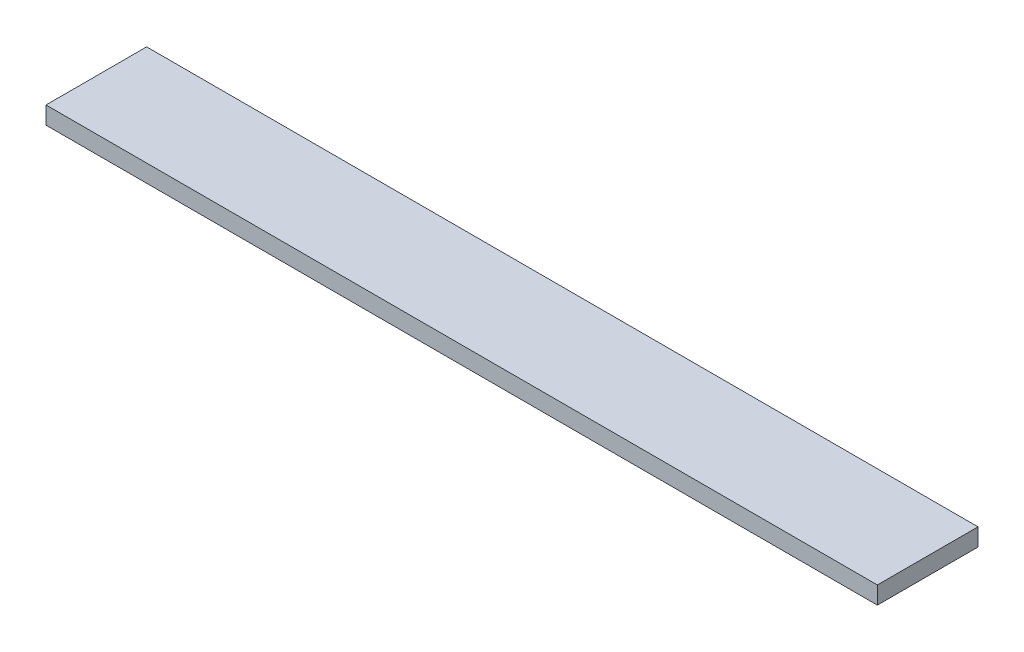
SolidWorks part; units mm, degrees
ref_plane "Front" through (0, 0, 0) normal (0, 0, 1) x (1, 0, 0)
ref_plane "Top" through (0, 0, 0) normal (0, 1, 0) x (1, 0, 0)
ref_plane "Right" through (0, 0, 0) normal (1, 0, 0) x (0, 0, -1)
sketch "Sketch1" plane through (0, 0, 0) normal (0, 1, 0) x (1, 0, 0)
  line L1 (-2413, 584.2) -> (2413, 584.2)
  line L2 (-2413, 584.2) -> (-2413, -584.2)
  line L3 (-2413, -584.2) -> (2413, -584.2)
  line L4 (2413, 584.2) -> (2413, -584.2)
  line L5 (-2413, 584.2) -> (2413, -584.2) construction
  line L6 (-2413, -584.2) -> (2413, 584.2) construction
  point P0 (0, 0)
  dimension "D1" = 4826
  dimension "D2" = 1168.4
extrude "Boss-Extrude1" add sketch "Sketch1" along normal blind 101.6
sketch "Sketch2" plane through (0, 101.6, 0) normal (0, 1, 0) x (1, 0, 0)
  line L0 (2413, -584.2) -> (2413, 584.2) construction
  line L1 (-2413, 584.2) -> (2413, 584.2)
  line L2 (-2413, 584.2) -> (-2413, 0)
  line L3 (-2413, 0) -> (2413, 0)
  line L4 (2413, 584.2) -> (2413, 0)
  line L5 (-2413, -584.2) -> (2413, -584.2) construction
  dimension "D1" = 584.2
extrude "Cut-Extrude1" cut sketch "Sketch2" against normal through all
sketch "Sketch4" [suppressed] plane through (0, 101.6, 0) normal (0, 1, 0) x (1, 0, 0)
  line L0 (2413, 584.2) -> (-2413, 584.2) construction
  line L1 (-2413, -584.2) -> (-2717.8, -584.2)
  line L2 (-2413, -584.2) -> (-2413, 584.2)
  line L3 (-2413, 584.2) -> (-2717.8, 584.2)
  line L4 (-2717.8, -584.2) -> (-2717.8, 584.2)
  line L5 (2413, -584.2) -> (2413, 584.2) construction
  dimension "D1" = 5130.8
extrude "Boss-Extrude2" [suppressed] add sketch "Sketch4" against normal up to surface (101.6 mm away) up to face at (0, 0, 292.1)
